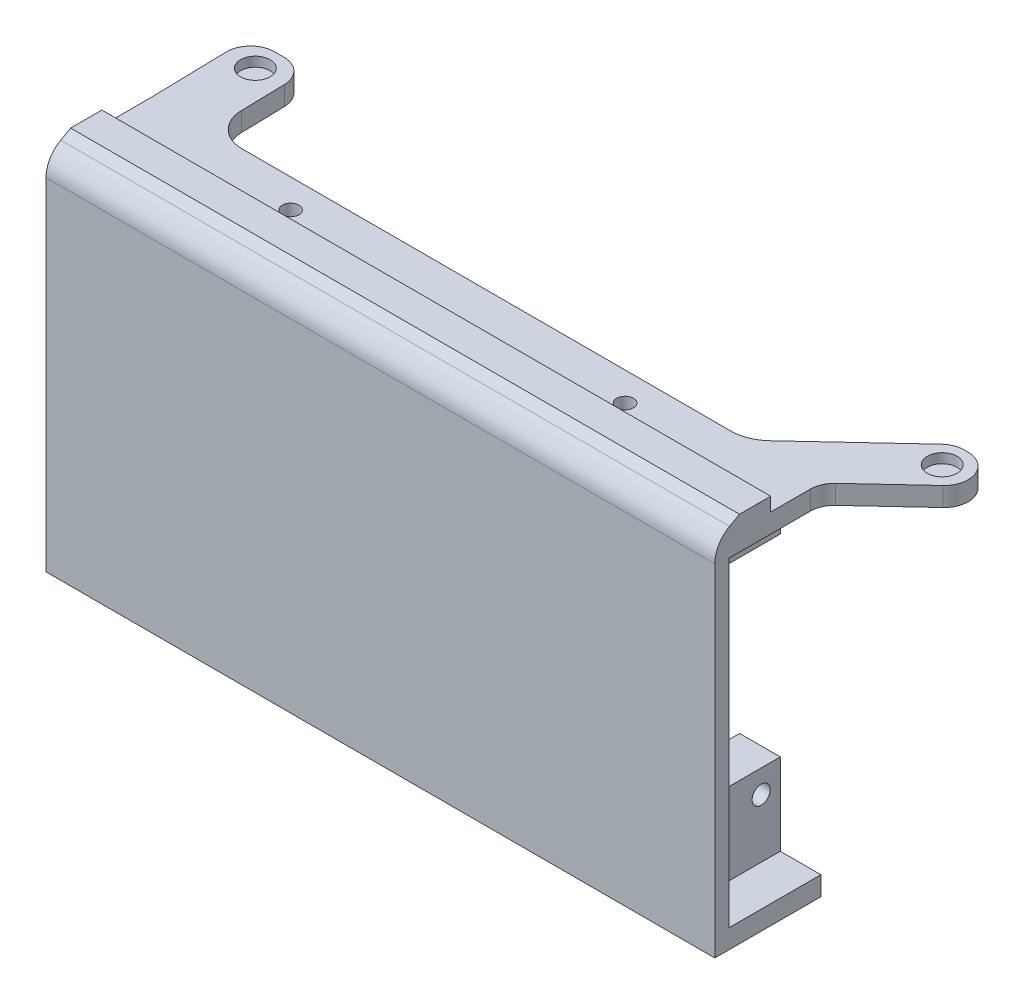
SolidWorks part; units mm, degrees
material "ABS"
ref_plane "Front Plane" through (0, 0, 0) normal (0, 0, 1) x (1, 0, 0)
ref_plane "Top Plane" through (0, 0, 0) normal (0, 1, 0) x (1, 0, 0)
ref_plane "Right Plane" through (0, 0, 0) normal (1, 0, 0) x (0, 0, -1)
sketch "Sketch1" plane through (0, 0, 0) normal (0, 0, 1) x (1, 0, 0)
  line L1 (-70, -37.5) -> (70, -37.5)
  line L2 (-70, -37.5) -> (-70, 37.5)
  line L3 (-70, 37.5) -> (70, 37.5)
  line L4 (70, -37.5) -> (70, 37.5)
  line L5 (-70, -37.5) -> (70, 37.5) construction
  line L6 (-70, 37.5) -> (70, -37.5) construction
  point P0 (0, 0)
  dimension "D1" = 75
  dimension "D2" = 140
extrude "Boss-Extrude1" add sketch "Sketch1" along normal blind 22.2
sketch "Sketch2" plane through (0, 0, 0) normal (0, 0, -1) x (-1, 0, 0)
  line L0 (-70, -37.5) -> (-70, 37.5) construction
  line L1 (-61.5, 24) -> (-53, 24)
  line L2 (-70, 20.2) -> (-70, -20.2)
  line L4 (70, 20.2) -> (70, -20.2)
  line L5 (70, 37.5) -> (70, -37.5) construction
  line L6 (-70, 0) -> (70, 0) construction
  line L7 (-61.5, 24) -> (-61.5, 33.5)
  line L9 (-53, 24) -> (-53, 33.5)
  line L10 (-53, 33.5) -> (53, 33.5)
  line L11 (53, 24) -> (53, 33.5)
  line L12 (-61.5, 33.5) -> (-70, 33.5)
  line L14 (-53, -16.4) -> (-53, -33.5)
  line L15 (-53, -33.5) -> (53, -33.5)
  line L16 (53, -16.4) -> (53, -33.5)
  line L17 (-61.5, -16.4) -> (-53, -16.4)
  line L18 (53, -16.4) -> (61.5, -16.4)
  line L19 (53, 24) -> (61.5, 24)
  line L20 (-70, 37.5) -> (70, 37.5) construction
  line L21 (70, -37.5) -> (-70, -37.5) construction
  line L22 (-70, 33.5) -> (-70, 20.2)
  line L23 (61.5, 24) -> (61.5, 33.5)
  line L24 (61.5, 33.5) -> (70, 33.5)
  line L25 (70, 33.5) -> (70, 20.2)
  line L26 (-61.5, -16.4) -> (-61.5, -33.5)
  line L27 (-61.5, -33.5) -> (-70, -33.5)
  line L28 (-70, -33.5) -> (-70, -20.2)
  line L29 (61.5, -16.4) -> (61.5, -33.5)
  line L30 (61.5, -33.5) -> (70, -33.5)
  line L31 (70, -33.5) -> (70, -20.2)
  dimension "D1" = 40.4
  dimension "D2" = 17
  dimension "D3" = 4
  dimension "D4" = 4
  dimension "D5" = 8.5
  dimension "D6" = 9.5
extrude "Cut-Extrude1" cut sketch "Sketch2" against normal offset from surface (19.2 mm away) 3 up to face at (0, 0, 22.2)
sketch "Sketch3" plane through (-70, 0, 0) normal (-1, 0, 0) x (0, 0, 1)
  line L0 (4, 28.25) -> (14, 28.25) construction
  line L1 (19.2, 33.5) -> (19.2, -33.5) construction
  line L2 (22.2, 37.5) -> (0, 37.5) construction
  line L3 (4, -21.25) -> (14, -21.25) construction
  line L8 (9, -21.25) -> (9, 28.25) construction
  circle A0 centre (14, 28.25) radius 1.9
  circle A1 centre (4, 28.25) radius 1.9
  circle A2 centre (4, -21.25) radius 1.9
  circle A3 centre (14, -21.25) radius 1.9115
  dimension "3.5" = 3.8
  dimension "D1" = 3.8
  dimension "D2" = 10
  dimension "D3" = 10
  dimension "D4" = 49.5
  dimension "D5" = 10.2
  dimension "D6" = 9.25
extrude "Cut-Extrude2" cut sketch "Sketch3" against normal through all both and the other way through all
sketch "Sketch4" plane through (0, 0, 19.2) normal (0, 0, -1) x (-1, 0, 0)
  line L0 (0, 33.5) -> (0, -33.5) construction
  line L1 (-53, 33.5) -> (53, 33.5) construction
  line L2 (53, -33.5) -> (-53, -33.5) construction
  line L3 (-77.5, -12.5) -> (77.5, -12.5) construction
  line L6 (-53, -33.5) -> (53, -33.5) construction
  circle A0 centre (-28, -3.5) radius 6.5
  circle A1 centre (28, -3.5) radius 6.5
  circle A2 centre (28, -21.5) radius 6.5
  circle A3 centre (-28, -21.5) radius 6.5
  dimension "D1" = 13
  dimension "D2" = 28
  dimension "D3" = 18
  dimension "D4" = 21
extrude "Boss-Extrude2" add sketch "Sketch4" along normal blind 14 draft 5
sketch "Sketch24" plane through (0, 0, 0) normal (1, 0, 0) x (0, 0, -1)
  line L0 (-5.2, -26.7752) -> (-15.3094, 8.4805)
  line L1 (-15.3094, 8.4805) -> (-1.271, 8.2972)
  line L2 (-1.271, 8.2972) -> (-5.2, -26.7752)
  line L3 (-5.2, -26.7752) -> (-5.2, 13.7762) construction
  dimension "D1" = 16
extrude "Cut-Extrude11" cut sketch "Sketch24" against normal blind 40 and the other way blind 40
sketch "Sketch5" plane through (0, -1.242, 12.5215) normal (0, 0.2756, -0.9613) x (-1, 0, 0)
  line L0 (-28.0022, 3.9031) -> (-28.0022, -8.295) construction
  circle A0 centre (-28.0022, -1.5969) radius 1.4
  circle A1 centre (27.9978, -1.5969) radius 1.4
  circle A2 centre (27.9978, -20.5969) radius 1.4
  circle A3 centre (-28.0022, -20.5969) radius 1.4
  ellipse E0 centre (-28, -2.196) end of major axis (-28, 3.9031) minor radius 5.8609 construction
  dimension "D1" = 19
  dimension "D4" = 2.8
  dimension "D5" = 5.5
  dimension "D2" = 2
  dimension "D3" = 2
extrude "Cut-Extrude3" cut sketch "Sketch5" against normal blind 6
sketch "Sketch25" plane through (0, 0, 19.2) normal (0, 0, -1) x (-1, 0, 0)
  line L0 (0, 0) -> (0, -33.5) construction
  line L1 (53, -33.5) -> (-53, -33.5) construction
  line L3 (-31.25, 7.8902) -> (31.25, 7.8902)
  line L4 (-31.25, 7.8902) -> (-31.25, -29.0728)
  line L5 (-31.25, -29.0728) -> (31.25, -29.0728)
  line L6 (31.25, 7.8902) -> (31.25, -29.0728)
  line L7 (-31.25, 7.8902) -> (31.25, -29.0728) construction
  line L8 (-31.25, -29.0728) -> (31.25, 7.8902) construction
  line L9 (-35.0668, 9.5643) -> (35.0668, 9.5643)
  line L10 (-35.0668, 9.5643) -> (-35.0668, -30.7468)
  line L11 (-35.0668, -30.7468) -> (35.0668, -30.7468)
  line L12 (35.0668, 9.5643) -> (35.0668, -30.7468)
  line L13 (-35.0668, 9.5643) -> (35.0668, -30.7468) construction
  line L14 (-35.0668, -30.7468) -> (35.0668, 9.5643) construction
  point P5 (0, -10.5913)
  point P10 (0, -10.5913)
  dimension "D1" = 62.5
extrude "Cut-Extrude12" cut sketch "Sketch25" along normal through all
sketch "Sketch6" plane through (0, 0, 0) normal (0, 0, -1) x (-1, 0, 0)
  line L14 (-53, -16.4) -> (-53, -33.5) construction
  line L15 (-70, -37.5) -> (-53, -37.5)
  line L16 (-70, -37.5) -> (-70, -29)
  line L17 (-70, -29) -> (-53, -29)
  line L18 (-53, -37.5) -> (-53, -29)
  line L19 (53, -33.5) -> (53, -16.4) construction
  line L20 (70, -37.5) -> (53, -37.5)
  line L21 (70, -37.5) -> (70, -29)
  line L22 (70, -29) -> (53, -29)
  line L23 (53, -37.5) -> (53, -29)
  dimension "D1" = 8.5
  dimension "D2" = 8.5
extrude "Boss-Extrude3" [suppressed] add sketch "Sketch6" along normal blind 14
sketch "Sketch8" [suppressed] plane through (77.5, 0, 0) normal (1, 0, 0) x (0, 0, -1)
  line L0 (14, -29) -> (0, -29) construction
  line L1 (1.5, -30.5) -> (9.5, -30.5)
  line L3 (2, -36) -> (9.5, -36)
  line L5 (-22.2, -37.5) -> (14, -37.5) construction
  line L6 (14, -29) -> (14, -37.5) construction
  line L7 (1.5, -30.5) -> (0, -30.5)
  line L8 (0, -30.5) -> (0, -36)
  line L9 (0, -36) -> (2, -36)
  arc A1 (9.5, -36) -> (9.5, -30.5) centre (9.5, -33.25) ccw
  dimension "D1" = 4.5
  dimension "D2" = 1.5
  dimension "D3" = 1.5
  dimension "D4" = 7.5
extrude "Cut-Extrude4" [suppressed] cut sketch "Sketch8" against normal up to surface (155 mm away)
fillet "Fillet1" [suppressed] radius 0.5
sketch "Sketch9" plane through (0, -33.5, 0) normal (0, 1, 0) x (1, 0, 0)
  line L0 (0, -19.2) -> (0, 0) construction
  line L1 (-53, -19.2) -> (53, -19.2) construction
  line L2 (53, 0) -> (-53, 0) construction
  circle A0 centre (35, -6) radius 1.75
  circle A1 centre (-35, -6) radius 1.75
  dimension "D1" = 3.5
  dimension "D2" = 6
  dimension "D3" = 35
extrude "Cut-Extrude5" cut sketch "Sketch9" against normal through all both and the other way through all
sketch "Sketch12" plane through (0, 37.5, 0) normal (0, 1, 0) x (1, 0, 0)
  line L0 (70, 0) -> (92.5197, 21)
  line L1 (92.5197, 21) -> (77.0197, 21)
  line L2 (77.0197, 21) -> (56.9914, 2.3232)
  line L3 (70, 0) -> (-70, 0) construction
  line L4 (58.0935, 0) -> (70, 0)
  line L5 (84.7697, 21) -> (64.0468, 0) construction
  line L7 (58.0935, 0) -> (51.0935, 0)
  line L8 (-70, 0) -> (-70.5, 21)
  line L9 (-70.5, 21) -> (-58.5, 21)
  line L10 (-58.5, 21) -> (-58.1627, 6.8334)
  line L11 (70, 0) -> (-70, 0) construction
  line L12 (-70, 0) -> (-51.1647, 0)
  line L13 (-64.5, 21) -> (-64, 0) construction
  line L14 (-70, -22.2) -> (-70, 0) construction
  arc A0 (51.0935, 0) -> (56.9914, 2.3232) centre (51.0935, 8.6479) ccw
  arc A1 (-58.1627, 6.8334) -> (-51.1647, 0) centre (-51.1647, 7) ccw
  dimension "D5" = 7
  dimension "D1" = 15.5
  dimension "D2" = 137
  dimension "D3" = 21
  dimension "D4" = 7
  dimension "D6" = 12
  dimension "D7" = 21
  dimension "D8" = 11.5
extrude "Boss-Extrude5" add sketch "Sketch12" against normal blind 4
fillet "Fillet4" radius 5 5 edges at (77.0197, 35.5, -21) (92.5197, 35.5, -21) (-58.5, 35.5, -21) (-70.5, 35.5, -21) (70, 35.5, 0)
sketch "Sketch13" plane through (0, 37.5, 0) normal (0, 1, 0) x (1, 0, 0)
  line L0 (79.8265, 21) -> (78.9893, 21) construction
  line L1 (71.59, 1.4827) -> (83.2365, 12.3432) construction
  line L2 (-70.3781, 15.881) -> (-70, 0) construction
  circle A0 centre (79.3866, 16) radius 3.1
  circle A1 centre (-64.3793, 16) radius 3.1
  dimension "D3" = 6.2
  dimension "D1" = 5
  dimension "D2" = 5.3
  dimension "D4" = 6
extrude "Cut-Extrude7" cut sketch "Sketch13" against normal blind 2
sketch "Sketch14" plane through (70, 0, 0) normal (1, 0, 0) x (0, 0, -1)
  line L0 (-22.2, 37.5) -> (-11.2, 43.6111) construction
  line L3 (-22.2, -37.5) -> (-22.2, 37.5) construction
  line L4 (-22.2, 37.5) -> (-16.602, 37.5)
  line L5 (-22.2, 37.5) -> (-17.0429, 40.3651)
  line L7 (-22.2, 37.5) -> (-2.1741, 37.5) construction
  line L8 (-17.0429, 40.3651) -> (-10.5, 40.3651)
  line L9 (-10.5, 40.3651) -> (-10.5, 37.5)
  line L10 (-10.5, 37.5) -> (-16.602, 37.5)
  dimension "D1" = 11
  dimension "D2" = 6.1111
  dimension "D3" = 11.7
extrude "Boss-Extrude6" add sketch "Sketch14" against normal up to surface (140 mm away) up to face at (-70, 0, 10.35)
fillet "Fillet5" radius 6 1 edges at (0, 37.5, 22.2)
sketch "Sketch17" plane through (0, -37.5, 0) normal (0, -1, 0) x (1, 0, 0)
  line L2 (86.593, -19.5) -> (67.593, -19.5)
  line L3 (67.593, -19.5) -> (58.5, 0)
  line L4 (-70, 0) -> (70, 0) construction
  line L5 (58.5, 0) -> (77.5, 0)
  line L10 (77.5, 0) -> (86.593, -19.5)
  line L11 (66.1941, -16.5) -> (85.1941, -16.5) construction
  circle A0 centre (66.593, -6.5) radius 1.75
  circle A1 centre (81.593, -16.5) radius 1.75
  dimension "D6" = 13
  dimension "D7" = 3.5
  dimension "D1" = 3
  dimension "D2" = 20
  dimension "D3" = 19
  dimension "D4" = 65
  dimension "D5" = 19.5
  dimension "D8" = 5
extrude "Boss-Extrude7" [suppressed] add sketch "Sketch17" against normal blind 4
sketch "Sketch18" [suppressed] plane through (0, 0, -19.5) normal (0, 0, -1) x (-1, 0, 0)
  line L1 (-67.593, -33.5) -> (-86.593, -33.5) construction
  line L3 (-86.593, -33.5) -> (-86.593, -37.5) construction
  arc A0 (-77.743, -33.5) -> (-74.443, -33.5) centre (-76.093, -33.5) ccw
  dimension "D1" = 1.65
  dimension "D2" = 10.5
extrude "Cut-Extrude9" [suppressed] cut sketch "Sketch18" against normal blind 10 and the other way through all
fillet "Fillet6" [suppressed] radius 2
sketch "Sketch19" plane through (0, 0, 0) normal (0, 0, -1) x (-1, 0, 0)
  line L1 (70, -37.5) -> (60.5, -37.5)
  line L2 (70, -37.5) -> (70, -27.5)
  line L3 (70, -27.5) -> (48, -27.5)
  line L4 (48, -37.5) -> (48, -27.5)
  line L7 (51.5, -37.5) -> (51.5, -30.5)
  line L8 (51.5, -30.5) -> (60.5, -30.5)
  line L9 (60.5, -37.5) -> (60.5, -30.5)
  line L10 (51.5, -37.5) -> (48, -37.5)
  dimension "D1" = 22
  dimension "D2" = 9
  dimension "D3" = 9.5
  dimension "D4" = 10
  dimension "D5" = 7
extrude "Boss-Extrude10" [suppressed] add sketch "Sketch19" along normal blind 19.5 and the other way up to next
sketch "Sketch20" [suppressed] plane through (0, -27.5, 0) normal (0, 1, 0) x (1, 0, 0)
  line L0 (-70, 19.5) -> (-48, 19.5) construction
  line L1 (-70, 19.5) -> (-70, -19.2) construction
  circle A0 centre (-66, 15.5) radius 1.95
  dimension "3.5" = 3.9
  dimension "D2" = 4
  dimension "D3" = 4
extrude "Cut-Extrude10" [suppressed] cut sketch "Sketch20" against normal blind 10
sketch "Sketch21" [suppressed] plane through (0, 0, 0) normal (0, 0, -1) x (-1, 0, 0)
  line L1 (51.5, -37.5) -> (60.5, -37.5)
  line L2 (51.5, -37.5) -> (51.5, -30.5)
  line L3 (51.5, -30.5) -> (60.5, -30.5)
  line L4 (60.5, -37.5) -> (60.5, -30.5)
extrude "Boss-Extrude11" [suppressed] add sketch "Sketch21" along normal offset from surface (11 mm away) 8.5
chamfer "Chamfer1" [suppressed] distance 6 angle 45
sketch "Sketch22" plane through (0, 0, 22.2) normal (0, 0, 1) x (1, 0, 0)
  circle A0 centre (-70, 31.616) radius 6
  circle A1 centre (70, 31.616) radius 6
  circle A2 centre (70, -37.5) radius 6
  circle A3 centre (-70, -37.5) radius 6
  dimension "D1" = 12
  dimension "D2" = 2.3536
  dimension "D3" = 2.3536
extrude "Boss-Extrude12" [suppressed] add sketch "Sketch22" against normal blind 0.1
sketch "Sketch23" plane through (0, -33.5, 0) normal (0, 1, 0) x (1, 0, 0)
  circle A0 centre (-35, -6) radius 3.5
  circle A1 centre (35, -6) radius 3.5
  circle A2 centre (35, -6) radius 1.75 construction
  circle A3 centre (-35, -6) radius 1.75 construction
  circle A4 centre (35, -6) radius 1.75
  circle A5 centre (-35, -6) radius 1.75
  dimension "D1" = 7
extrude "Boss-Extrude13" add sketch "Sketch23" along normal blind 1.5
fillet "Fillet7" radius 3 4 edges at (21.5, -21.5, 19.2) (-21.5, -21.5, 19.2) (-21.5, -3.5, 19.2) (21.5, -3.5, 19.2)
chamfer "Chamfer2" distance 1.5 distance2 1 2 edges at (-35, -32, 9.5) (35, -32, 9.5) first distance on face at (-35, -32, 9.5) first distance on face at (35, -32, 9.5)
equation "\"D6@Sketch3\"=12.75-3.5mm"
